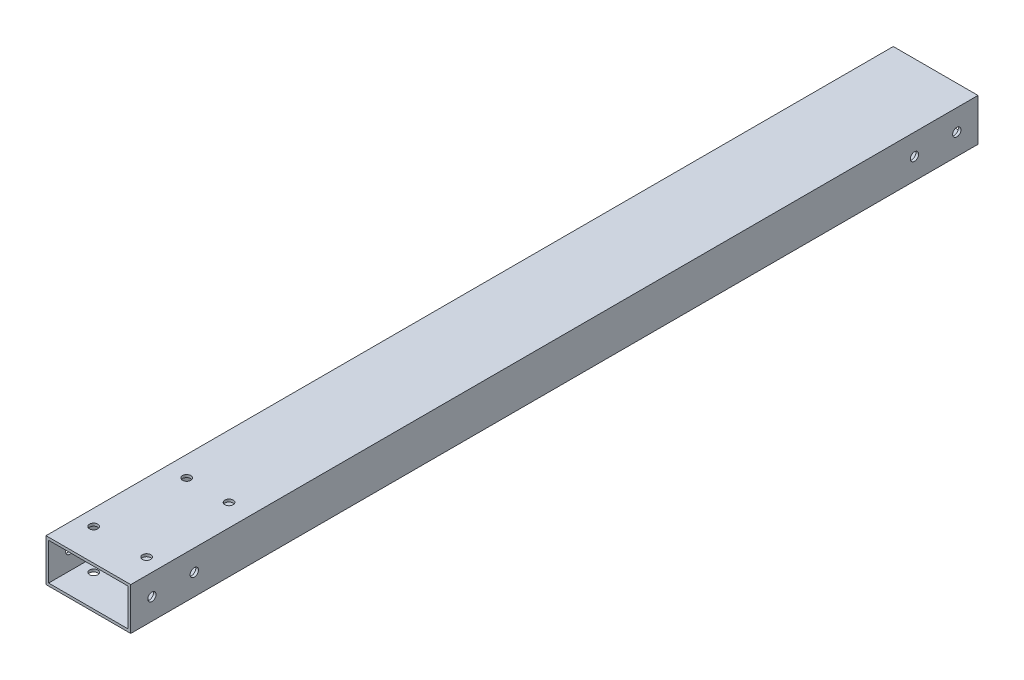
SolidWorks part; units mm, degrees
ref_plane "Front Plane" through (0, 0, 0) normal (0, 0, 1) x (1, 0, 0)
ref_plane "Top Plane" through (0, 0, 0) normal (0, 1, 0) x (1, 0, 0)
ref_plane "Right Plane" through (0, 0, 0) normal (1, 0, 0) x (0, 0, -1)
sketch "Sketch1" plane through (0, 0, 0) normal (0, 0, 1) x (1, 0, 0)
  line L0 (-23.8125, 11.1125) -> (23.8125, 11.1125)
  line L2 (-25.4, 12.7) -> (25.4, 12.7)
  line L3 (-25.4, 12.7) -> (-25.4, -12.7)
  line L4 (-25.4, -12.7) -> (25.4, -12.7)
  line L5 (25.4, 12.7) -> (25.4, -12.7)
  line L10 (23.8125, 11.1125) -> (23.8125, -11.1125)
  line L11 (-23.8125, -11.1125) -> (23.8125, -11.1125)
  line L12 (-23.8125, 11.1125) -> (-23.8125, -11.1125)
  point P12 (0, 12.7)
  point P14 (25.4, 0)
  dimension "Wall Thickness" = 1.5875
  dimension "Outside Width" = 50.8
  dimension "Outside Height" = 25.4
  dimension "Inside Height" = 22.225
  dimension "Inside Width" = 47.625
sketch "Sketch2" plane through (0, 0, 0) normal (1, 0, 0) x (0, 0, -1)
  line L0 (254, 0) -> (-254, 0)
  point P4 (0, 0)
  point P7 (-254, 0)
  point P10 (254, 0)
  dimension "Length" = 508
sketch "Sketch3" plane through (0, 0, 0) normal (0, 0, 1) x (1, 0, 0)
  line L21 (25.4, 12.7) -> (-25.4, 12.7)
  line L22 (25.4, -12.7) -> (25.4, 12.7)
  line L23 (-25.4, -12.7) -> (25.4, -12.7)
  line L24 (-25.4, 12.7) -> (-25.4, -12.7)
  line L25 (25.4, 12.7) -> (-25.4, 12.7)
  line L26 (25.4, -12.7) -> (25.4, 12.7)
  line L27 (-25.4, -12.7) -> (25.4, -12.7)
  line L28 (-25.4, 12.7) -> (-25.4, -12.7)
  line L29 (23.8125, 11.1125) -> (-23.8125, 11.1125)
  line L30 (23.8125, -11.1125) -> (23.8125, 11.1125)
  line L31 (-23.8125, -11.1125) -> (23.8125, -11.1125)
  line L32 (-23.8125, 11.1125) -> (-23.8125, -11.1125)
  line L33 (23.8125, 11.1125) -> (-23.8125, 11.1125)
  line L34 (23.8125, -11.1125) -> (23.8125, 11.1125)
  line L35 (-23.8125, -11.1125) -> (23.8125, -11.1125)
  line L36 (-23.8125, 11.1125) -> (-23.8125, -11.1125)
  dimension "D1" = 0
  dimension "D2" = 0
extrude "Boss-Extrude1" add sketch "Sketch3" along normal up to vertex (254 mm away) and the other way up to vertex (254 mm away) up to point (0, 0, 254) other way up to point (0, 0, -254)
sketch "Drawing Reference" plane through (0, 0, 0) normal (1, 0, 0) x (0, 0, -1)
  line L0 (-254, 0) -> (254, 0) construction
  line L1 (0, -12.7) -> (0, 12.7) construction
  line L2 (-254, -12.7) -> (254, -12.7) construction
  line L5 (-254, 12.7) -> (254, 12.7) construction
  point P7 (-217.424, 0)
  point P8 (217.424, 0)
  dimension "D1" = 36.576
hole_wizard "#10 Clearance Hole1" positions "Sketch4" profile "Sketch5" hole size "#10" standard "ANSI Inch" end condition through all
sketch "Sketch4" plane through (25.4, 0, 0) normal (1, 0, 0) x (0, 0, -1)
  point P0 (-241.3, 0)
  point P3 (-215.9, 0)
  point P6 (215.9, 0)
  point P9 (241.3, 0)
sketch "Sketch5" plane through (25.4, 0, 241.3) normal (0, 1, 0) x (0, 0, -1)
  line L0 (0, 0) -> (0, 50.8)
  line L1 (0, 50.8) -> (2.4892, 50.8)
  line L2 (2.4892, 50.8) -> (2.4892, 0)
  line L5 (2.4892, 0) -> (0, 0)
  line L11 (0, -6.35) -> (0, 107.95) construction
  dimension "Thru Hole Dia." = 4.9784
  dimension "Thru Hole Depth" = 50.8
sketch "Sketch6" plane through (0, 12.7, 0) normal (0, 1, 0) x (1, 0, 0)
  line L1 (-13.208, -181.8469) -> (12.192, -181.8469) construction
  circle A0 centre (-13.208, -181.8469) radius 2.4892 construction
  circle A1 centre (12.192, -181.8469) radius 2.4892 construction
hole_wizard "#10 Clearance Hole2" positions "Sketch9" profile "Sketch10" hole size "#10" standard "ANSI Inch" end condition through all
sketch "Sketch9" plane through (0, 12.7, 0) normal (0, 1, 0) x (1, 0, 0)
  point P6 (-13.208, -181.8469)
  point P9 (12.192, -181.8469)
  point P12 (-15.875, -234.95)
  point P15 (15.875, -234.95)
sketch "Sketch10" plane through (-13.208, 12.7, 181.8469) normal (1, 0, 0) x (0, 0, 1)
  line L0 (0, 0) -> (0, 25.4)
  line L1 (0, 25.4) -> (2.4892, 25.4)
  line L2 (2.4892, 25.4) -> (2.4892, 0)
  line L5 (2.4892, 0) -> (0, 0)
  line L11 (0, -6.35) -> (0, 107.95) construction
  dimension "Thru Hole Dia." = 4.9784
  dimension "Thru Hole Depth" = 25.4
equation "\"D1@Drawing Reference\"=\"Outside Width@Sketch1\" * 0.72"
